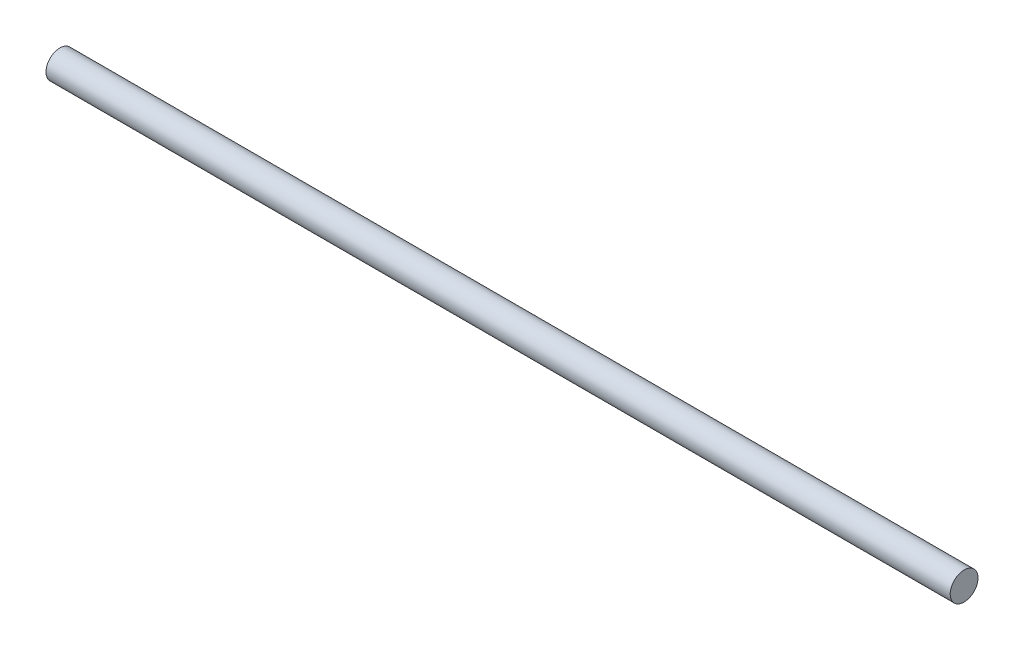
SolidWorks part; units mm, degrees
material "AISI 1020"
ref_plane "Plano frontal" through (0, 0, 0) normal (0, 0, 1) x (1, 0, 0)
ref_plane "Plano superior" through (0, 0, 0) normal (0, 1, 0) x (1, 0, 0)
ref_plane "Plano direito" through (0, 0, 0) normal (1, 0, 0) x (0, 0, -1)
sketch "Esboço1" plane through (0, 0, 0) normal (0, 0, 1) x (1, 0, 0)
  line L0 (0, 0) -> (0, 2)
  line L3 (0, 2) -> (130, 2)
  line L4 (130, 2) -> (130, 0)
  line L5 (130, 0) -> (0, 0)
  dimension "D1" = 130
  dimension "D3" = 2
revolve "Revolução1" add sketch "Esboço1" angle 360 about L5
cosmetic thread "Representação de rosca1" parameters "D2"=3.22
cosmetic thread "Representação de rosca2" parameters "D2"=3.22
sketch "Esboço2" plane through (130, 0, 0) normal (1, 0, 0) x (0, 0, -1)
  circle A0 centre (0, 0) radius 2
  dimension "D1" = 4
curve "Hélice/Espiral1" [suppressed] pitch 0.8 height 118 turns 147.5
sketch "Esboço3" plane through (0, 0, 0) normal (0, 0, 1) x (1, 0, 0)
  line L0 (130, 2) -> (130.75, 2)
  line L1 (130.75, 2) -> (130.375, 1.7)
  line L2 (130.375, 1.7) -> (130, 2)
  dimension "D1" = 0.75
  dimension "D2" = 0.3
  dimension "D3" = 0.375
sweep "Varredura de corte1" [suppressed] cut profiles "Esboço3" path "Hélice/Espiral1"
